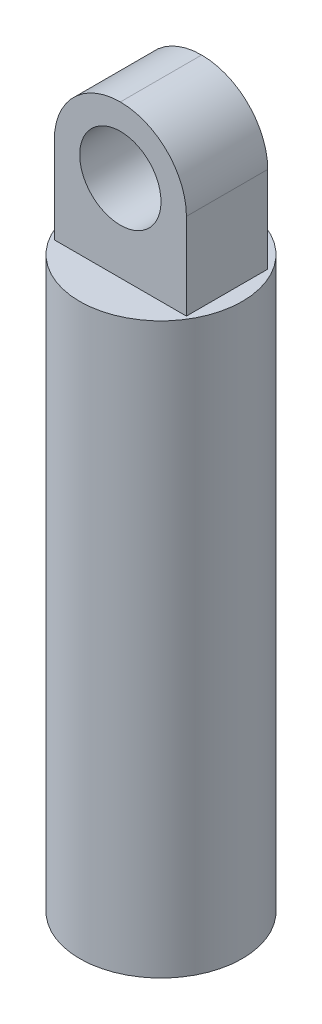
SolidWorks part; units mm, degrees
material "6061 Alloy"
ref_plane "Front Plane" through (0, 0, 0) normal (0, 0, 1) x (1, 0, 0)
ref_plane "Top Plane" through (0, 0, 0) normal (0, 1, 0) x (1, 0, 0)
ref_plane "Right Plane" through (0, 0, 0) normal (1, 0, 0) x (0, 0, -1)
sketch "Sketch1" plane through (0, 0, 0) normal (0, 1, 0) x (1, 0, 0)
  circle A0 centre (0, 0) radius 12.7
  dimension "D1" = 25.4
extrude "Extrude1" add sketch "Sketch1" along normal blind 88.9
sketch "Sketch2" plane through (0, 88.9, 0) normal (0, 1, 0) x (-1, 0, 0)
  line L0 (-10.3187, -6.35) -> (10.3188, -6.35)
  line L1 (-10.3187, 6.35) -> (10.3187, 6.35)
  line L2 (-10.3187, 6.35) -> (-10.3187, -6.35)
  line L3 (10.3187, 6.35) -> (10.3188, -6.35)
  dimension "D1" = 12.7
  dimension "D2" = 6.35
  dimension "D3" = 20.6375
  dimension "D4" = 10.3187
extrude "Extrude2" add sketch "Sketch2" along normal blind 23.8125
fillet "Fillet1" radius 10.3187 2 edges at (-10.3188, 112.7125, 0) (10.3187, 112.7125, 0)
sketch "Sketch3" plane through (0, 0, 6.35) normal (0, 0, 1) x (1, 0, 0)
  circle A0 centre (0, 102.3937) radius 6.35
  arc A2 (0, 112.7125) -> (-10.3188, 102.3937) centre (0, 102.3937) ccw construction
  arc A3 (0, 112.7125) -> (-10.3188, 102.3937) centre (0, 102.3937) ccw construction
  dimension "D1" = 12.7
extrude "Cut-Extrude1" cut sketch "Sketch3" against normal through all
sketch "Sketch4" plane through (0, 0, 0) normal (0, 0, 1) x (1, 0, 0)
  circle A0 centre (0, 102.3937) radius 6.35 construction
  circle A1 centre (0, 102.3937) radius 6.35
